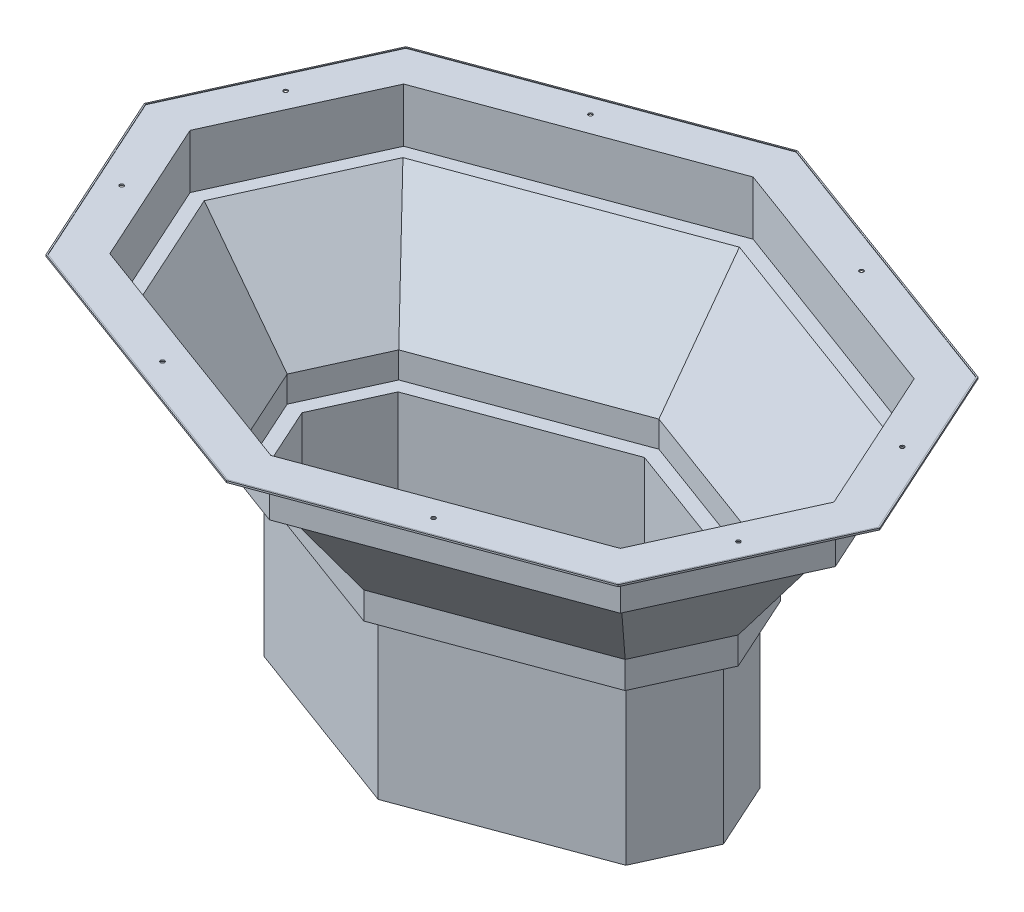
SolidWorks part; units mm, degrees
material "AISI 1020"
ref_plane "Front Plane" through (0, 0, 0) normal (0, 0, 1) x (1, 0, 0)
ref_plane "Top Plane" through (0, 0, 0) normal (0, 1, 0) x (1, 0, 0)
ref_plane "Right Plane" through (0, 0, 0) normal (1, 0, 0) x (0, 0, -1)
sketch "Sketch1" plane through (0, 0, 0) normal (0, 1, 0) x (1, 0, 0)
  line L0 (0, 0) -> (0, 457.2) construction
  line L1 (-609.6, 0) -> (-483.0506, 278.8894)
  line L2 (-609.6, 0) -> (0, 0) construction
  line L3 (483.0506, -278.8894) -> (-483.0506, -278.8894) construction
  line L4 (483.0506, -278.8894) -> (483.0506, 278.8894) construction
  line L5 (483.0506, 278.8894) -> (-483.0506, 278.8894) construction
  line L6 (-483.0506, -278.8894) -> (-483.0506, 278.8894) construction
  line L7 (483.0506, -278.8894) -> (-483.0506, 278.8894) construction
  line L8 (483.0506, 278.8894) -> (-483.0506, -278.8894) construction
  line L9 (-483.0506, 278.8894) -> (0, 457.2)
  line L10 (0, 457.2) -> (483.0506, 278.8894)
  line L11 (483.0506, 278.8894) -> (609.6, 0)
  line L12 (609.6, 0) -> (483.0506, -278.8894)
  line L13 (483.0506, -278.8894) -> (0, -457.2)
  line L14 (0, -457.2) -> (-483.0506, -278.8894)
  line L15 (-609.6, 0) -> (-483.0506, -278.8894)
  ellipse E0 centre (0, 0) end of major axis (-609.6, 0) minor radius 457.2 construction
  dimension "D1" = 609.6
  dimension "D2" = 457.2
  dimension "D3" = 30
extrude "Boss-Extrude1" add sketch "Sketch1" against normal blind 101.6
sketch "Sketch3" plane through (0, -101.6, 0) normal (0, -1, 0) x (1, 0, 0)
  line L0 (-464.3036, -258.7343) -> (0, -430.1247)
  line L1 (0, -430.1247) -> (464.3036, -258.7343)
  line L2 (464.3036, -258.7343) -> (581.7074, 0)
  line L3 (581.7074, 0) -> (464.3036, 258.7343)
  line L4 (464.3036, 258.7343) -> (0, 430.1247)
  line L5 (0, 430.1247) -> (-464.3036, 258.7343)
  line L6 (-464.3036, 258.7343) -> (-581.7074, 0)
  line L7 (-581.7074, 0) -> (-464.3036, -258.7343)
  line L8 (-483.0506, -278.8894) -> (0, -457.2)
  line L9 (0, -457.2) -> (483.0506, -278.8894)
  line L10 (483.0506, -278.8894) -> (609.6, 0)
  line L11 (609.6, 0) -> (483.0506, 278.8894)
  line L12 (483.0506, 278.8894) -> (0, 457.2)
  line L13 (0, 457.2) -> (-483.0506, 278.8894)
  line L14 (-483.0506, 278.8894) -> (-609.6, 0)
  line L15 (-609.6, 0) -> (-483.0506, -278.8894)
  line L16 (-483.0506, -278.8894) -> (0, -457.2) construction
  line L17 (0, -457.2) -> (483.0506, -278.8894) construction
  line L18 (483.0506, -278.8894) -> (609.6, 0) construction
  line L19 (609.6, 0) -> (483.0506, 278.8894) construction
  line L20 (483.0506, 278.8894) -> (0, 457.2) construction
  line L21 (0, 457.2) -> (-483.0506, 278.8894) construction
  line L22 (-483.0506, 278.8894) -> (-609.6, 0) construction
  line L23 (-609.6, 0) -> (-483.0506, -278.8894) construction
  dimension "D1" = 0
  dimension "D2" = 25.4
ref_plane "Plane1" through (0, -304.8, 0) normal (0, -1, 0) x (-1, 0, 0)
sketch "Sketch2" plane through (0, -304.8, 0) normal (0, -1, 0) x (-1, 0, 0)
  line L0 (0, 279.4925) -> (-360.0052, 146.6021)
  line L1 (-360.0052, 146.6021) -> (-426.5277, 0)
  line L2 (-426.5277, 0) -> (-360.0052, -146.6021)
  line L3 (-360.0052, -146.6021) -> (0, -279.4925)
  line L4 (0, -279.4925) -> (360.0052, -146.6021)
  line L5 (360.0052, -146.6021) -> (426.5277, 0)
  line L6 (426.5277, 0) -> (360.0052, 146.6021)
  line L7 (360.0052, 146.6021) -> (0, 279.4925)
  line L8 (483.0506, 278.8894) -> (0, 457.2)
  line L9 (609.6, 0) -> (483.0506, 278.8894)
  line L10 (483.0506, -278.8894) -> (609.6, 0)
  line L11 (0, -457.2) -> (483.0506, -278.8894)
  line L12 (-483.0506, -278.8894) -> (0, -457.2)
  line L13 (-609.6, 0) -> (-483.0506, -278.8894)
  line L14 (-483.0506, 278.8894) -> (-609.6, 0)
  line L15 (0, 457.2) -> (-483.0506, 278.8894)
  line L16 (483.0506, 278.8894) -> (0, 457.2) construction
  line L17 (609.6, 0) -> (483.0506, 278.8894) construction
  line L18 (483.0506, -278.8894) -> (609.6, 0) construction
  line L19 (0, -457.2) -> (483.0506, -278.8894) construction
  line L20 (-483.0506, -278.8894) -> (0, -457.2) construction
  line L21 (-609.6, 0) -> (-483.0506, -278.8894) construction
  line L22 (-483.0506, 278.8894) -> (-609.6, 0) construction
  line L23 (0, 457.2) -> (-483.0506, 278.8894) construction
  dimension "D2" = 177.7075
  dimension "D3" = 166.712
  dimension "D4" = 166.712
  dimension "D5" = 166.712
  dimension "D6" = 166.712
  dimension "D7" = 166.712
  dimension "D8" = 166.712
  dimension "D9" = 166.712
  dimension "D1" = 0
loft "Loft1" add profiles "Sketch3", "Sketch2" connector at (-464.3036, -101.6, 258.7343) connector at (-360.0052, -304.8, 146.6021)
sketch "Sketch4" plane through (0, -304.8, 0) normal (0, -1, 0) x (1, 0, 0)
  line L8 (0, -279.4925) -> (360.0052, -146.6021)
  line L9 (0, -279.4925) -> (360.0052, -146.6021)
  line L10 (360.0052, -146.6021) -> (426.5277, 0)
  line L11 (360.0052, -146.6021) -> (426.5277, 0)
  line L12 (426.5277, 0) -> (360.0052, 146.6021)
  line L13 (426.5277, 0) -> (360.0052, 146.6021)
  line L14 (360.0052, 146.6021) -> (0, 279.4925)
  line L15 (360.0052, 146.6021) -> (0, 279.4925)
  line L16 (0, 279.4925) -> (-360.0052, 146.6021)
  line L17 (0, 279.4925) -> (-360.0052, 146.6021)
  line L18 (-360.0052, 146.6021) -> (-426.5277, 0)
  line L19 (-360.0052, 146.6021) -> (-426.5277, 0)
  line L20 (-426.5277, 0) -> (-360.0052, -146.6021)
  line L21 (-426.5277, 0) -> (-360.0052, -146.6021)
  line L22 (-360.0052, -146.6021) -> (0, -279.4925)
  line L23 (-360.0052, -146.6021) -> (0, -279.4925)
  dimension "D1" = 0
extrude "Boss-Extrude2" add sketch "Sketch4" along normal blind 50.8
sketch "Sketch5" plane through (0, 0, 0) normal (0, 1, 0) x (1, 0, 0)
  line L0 (0, 538.4258) -> (-539.2916, 339.3547)
  line L1 (-539.2916, 339.3547) -> (-693.2779, 0)
  line L2 (-693.2779, 0) -> (-539.2916, -339.3547)
  line L3 (-539.2916, -339.3547) -> (0, -538.4258)
  line L4 (0, -538.4258) -> (539.2916, -339.3547)
  line L5 (539.2916, -339.3547) -> (693.2779, 0)
  line L6 (693.2779, 0) -> (539.2916, 339.3547)
  line L7 (539.2916, 339.3547) -> (0, 538.4258)
  line L8 (0, 457.2) -> (-483.0506, 278.8894)
  line L9 (-483.0506, 278.8894) -> (-609.6, 0)
  line L10 (-609.6, 0) -> (-483.0506, -278.8894)
  line L11 (-483.0506, -278.8894) -> (0, -457.2)
  line L12 (0, -457.2) -> (483.0506, -278.8894)
  line L13 (483.0506, -278.8894) -> (609.6, 0)
  line L14 (609.6, 0) -> (483.0506, 278.8894)
  line L15 (483.0506, 278.8894) -> (0, 457.2)
  line L16 (0, 457.2) -> (-483.0506, 278.8894) construction
  line L17 (-483.0506, 278.8894) -> (-609.6, 0) construction
  line L18 (-609.6, 0) -> (-483.0506, -278.8894) construction
  line L19 (-483.0506, -278.8894) -> (0, -457.2) construction
  line L20 (0, -457.2) -> (483.0506, -278.8894) construction
  line L21 (483.0506, -278.8894) -> (609.6, 0) construction
  line L22 (609.6, 0) -> (483.0506, 278.8894) construction
  line L23 (483.0506, 278.8894) -> (0, 457.2) construction
  dimension "D1" = 0
  dimension "D2" = 76.2
extrude "Boss-Extrude3" add sketch "Sketch5" along normal blind 3.175
sketch "Sketch6" plane through (0, -355.6, 0) normal (0, -1, 0) x (1, 0, 0)
  line L0 (0, 252.4172) -> (-341.2582, 126.447)
  line L1 (-341.2582, 126.447) -> (-398.6351, 0)
  line L2 (-398.6351, 0) -> (-341.2582, -126.447)
  line L3 (-341.2582, -126.447) -> (0, -252.4172)
  line L4 (0, -252.4172) -> (341.2582, -126.447)
  line L5 (341.2582, -126.447) -> (398.6351, 0)
  line L6 (398.6351, 0) -> (341.2582, 126.447)
  line L7 (341.2582, 126.447) -> (0, 252.4172)
  line L8 (360.0052, -146.6021) -> (426.5277, 0)
  line L9 (426.5277, 0) -> (360.0052, 146.6021)
  line L10 (360.0052, 146.6021) -> (0, 279.4925)
  line L11 (0, 279.4925) -> (-360.0052, 146.6021)
  line L12 (-360.0052, 146.6021) -> (-426.5277, 0)
  line L13 (-426.5277, 0) -> (-360.0052, -146.6021)
  line L14 (-360.0052, -146.6021) -> (0, -279.4925)
  line L15 (0, -279.4925) -> (360.0052, -146.6021)
  line L16 (360.0052, -146.6021) -> (426.5277, 0) construction
  line L17 (426.5277, 0) -> (360.0052, 146.6021) construction
  line L18 (360.0052, 146.6021) -> (0, 279.4925) construction
  line L19 (0, 279.4925) -> (-360.0052, 146.6021) construction
  line L20 (-360.0052, 146.6021) -> (-426.5277, 0) construction
  line L21 (-426.5277, 0) -> (-360.0052, -146.6021) construction
  line L22 (-360.0052, -146.6021) -> (0, -279.4925) construction
  line L23 (0, -279.4925) -> (360.0052, -146.6021) construction
  dimension "D1" = 0
  dimension "D2" = 25.4
extrude "Boss-Extrude4" add sketch "Sketch6" along normal blind 304.8
shell "Shell2" thickness 2.3813 removed face at (0, 3.175, 0)
sketch "Sketch7" [suppressed] plane through (0, 0, 0) normal (0, 1, 0) x (1, 0, 0)
  line L0 (-357.6619, 144.0827) -> (0, 276.108) construction
  line L1 (-423.0411, 0) -> (-357.6619, 144.0827) construction
  line L2 (-357.6619, -144.0827) -> (-423.0411, 0) construction
  line L3 (-357.6619, -144.0827) -> (0, -276.108) construction
  line L4 (0, -276.108) -> (357.6619, -144.0827) construction
  line L5 (357.6619, -144.0827) -> (423.0411, 0) construction
  line L6 (357.6619, 144.0827) -> (423.0411, 0) construction
  line L7 (357.6619, 144.0827) -> (0, 276.108) construction
  line L8 (-357.6619, 144.0827) -> (0, 276.108) construction
  line L9 (-423.0411, 0) -> (-357.6619, 144.0827) construction
  line L10 (-357.6619, -144.0827) -> (-423.0411, 0) construction
  line L11 (-357.6619, -144.0827) -> (0, -276.108) construction
  line L12 (0, -276.108) -> (357.6619, -144.0827) construction
  line L13 (357.6619, -144.0827) -> (423.0411, 0) construction
  line L14 (357.6619, 144.0827) -> (423.0411, 0) construction
  line L15 (357.6619, 144.0827) -> (0, 276.108) construction
sketch "Sketch8" plane through (0, 3.175, 0) normal (0, 1, 0) x (1, 0, 0)
  line L0 (511.1711, 309.122) -> (0, 497.8129) construction
  line L1 (0, 497.8129) -> (-511.1711, 309.122) construction
  line L2 (-511.1711, 309.122) -> (-651.4389, 0) construction
  line L3 (-651.4389, 0) -> (-511.1711, -309.122) construction
  line L4 (-511.1711, -309.122) -> (0, -497.8129) construction
  line L5 (0, -497.8129) -> (511.1711, -309.122) construction
  line L6 (511.1711, -309.122) -> (651.4389, 0) construction
  line L7 (651.4389, 0) -> (511.1711, 309.122) construction
  line L8 (539.2916, 339.3547) -> (0, 538.4258)
  line L9 (0, 538.4258) -> (-539.2916, 339.3547)
  line L10 (-539.2916, 339.3547) -> (-693.2779, 0)
  line L11 (-693.2779, 0) -> (-539.2916, -339.3547)
  line L12 (-539.2916, -339.3547) -> (0, -538.4258)
  line L13 (0, -538.4258) -> (539.2916, -339.3547)
  line L14 (539.2916, -339.3547) -> (693.2779, 0)
  line L15 (693.2779, 0) -> (539.2916, 339.3547)
  line L16 (539.2916, 339.3547) -> (0, 538.4258) construction
  line L17 (0, 538.4258) -> (-539.2916, 339.3547) construction
  line L18 (-539.2916, 339.3547) -> (-693.2779, 0) construction
  line L19 (-693.2779, 0) -> (-539.2916, -339.3547) construction
  line L20 (-539.2916, -339.3547) -> (0, -538.4258) construction
  line L21 (0, -538.4258) -> (539.2916, -339.3547) construction
  line L22 (539.2916, -339.3547) -> (693.2779, 0) construction
  line L23 (693.2779, 0) -> (539.2916, 339.3547) construction
  circle A0 centre (-255.5855, 403.4675) radius 3.81
  circle A1 centre (255.5855, 403.4675) radius 3.81
  circle A2 centre (581.305, 154.561) radius 3.81
  circle A3 centre (581.305, -154.561) radius 3.81
  circle A4 centre (255.5855, -403.4675) radius 3.81
  circle A5 centre (-255.5855, -403.4675) radius 3.81
  circle A6 centre (-581.305, -154.561) radius 3.81
  circle A7 centre (-581.305, 154.561) radius 3.81
  dimension "D3" = 7.62
  dimension "D1" = 0
  dimension "D2" = 38.1
extrude "Cut-Extrude1" cut sketch "Sketch8" against normal up to next
sketch "Sketch9" plane through (0, -660.4, 0) normal (0, -1, 0) x (1, 0, 0)
  line L1 (1009.9465, -645.8443) -> (-874.8808, -645.8443)
  line L2 (1009.9465, -645.8443) -> (1009.9465, 608.3567)
  line L3 (1009.9465, 608.3567) -> (-874.8808, 608.3567)
  line L4 (-874.8808, -645.8443) -> (-874.8808, 608.3567)
extrude "Boss-Extrude5" [suppressed] add sketch "Sketch9" against normal blind 495.3 separate body
combine bodies "Combine1" [suppressed] operation type subtract main body 107 bodies to subtract 106
